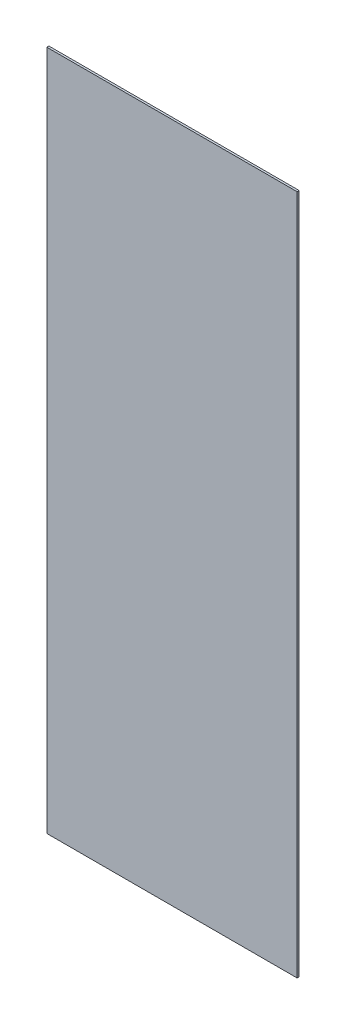
SolidWorks part; units mm, degrees
ref_plane "Front Plane" through (0, 0, 0) normal (0, 0, 1) x (1, 0, 0)
ref_plane "Top Plane" through (0, 0, 0) normal (0, 1, 0) x (1, 0, 0)
ref_plane "Right Plane" through (0, 0, 0) normal (1, 0, 0) x (0, 0, -1)
sketch "Sketch2" plane through (0, 0, 0) normal (0, 0, 1) x (1, 0, 0)
  line L1 (-73.7159, -2.6637) -> (73.7159, -2.6637)
  line L2 (-73.7159, -2.6637) -> (-73.7159, -403.7363)
  line L3 (-73.7159, -403.7363) -> (73.7159, -403.7363)
  line L4 (73.7159, -2.6637) -> (73.7159, -403.7363)
base flange "Base-Flange1" sketch "Sketch2" thickness 1.2141 reverse thickness direction yes parameters "D1"=1.27
sketch "Bend-Lines1" [suppressed] plane through (0, 0, 0) normal (0, 1, 0) x (1, 0, 0)
sketch "Bounding-Box1" [suppressed] plane through (0, 0, 0) normal (0, 1, 0) x (1, 0, 0)
sheet metal parameters "Sheet-Metal1" thickness 1.2141 parameters "D1"=1.27
flat pattern "Flat-Pattern1" [suppressed]
sketch "Bend-Lines2" plane through (0, 0, 0) normal (0, 1, 0) x (1, 0, 0)
sketch3d "Bounding-Box2" [suppressed]
  line L0 (73.7159, -2.6637, 0) -> (73.7159, -403.7363, 0) construction
  line L1 (-73.7159, -2.6637, 0) -> (-73.7159, -403.7363, 0) construction
  line L2 (73.7159, -2.6637, 0) -> (-73.7159, -2.6637, 0) construction
  line L3 (73.7159, -403.7363, 0) -> (-73.7159, -403.7363, 0) construction
